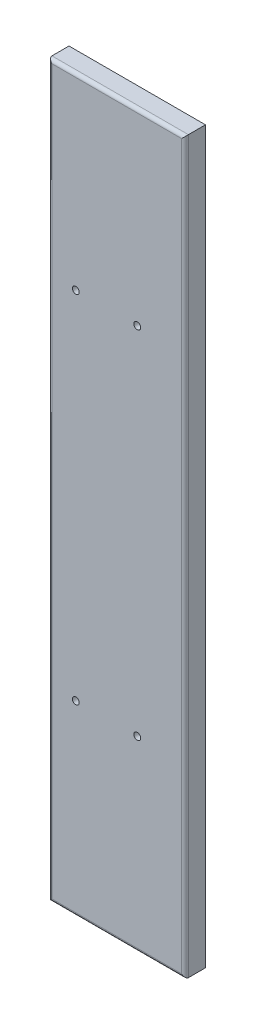
SolidWorks part; units mm, degrees
material "Pine"
ref_plane "Front Plane" through (0, 0, 0) normal (0, 0, 1) x (1, 0, 0)
ref_plane "Top Plane" through (0, 0, 0) normal (0, 1, 0) x (1, 0, 0)
ref_plane "Right Plane" through (0, 0, 0) normal (1, 0, 0) x (0, 0, -1)
sketch "Sketch1" plane through (0, 0, 0) normal (0, 0, 1) x (1, 0, 0)
  line L0 (-50.8, 25.4) -> (-53.975, 25.4)
  line L2 (-53.975, 174.625) -> (73.025, 174.625)
  line L3 (73.025, 174.625) -> (73.025, -504.825)
  line L4 (73.025, -504.825) -> (-53.975, -504.825)
  line L6 (-53.975, -504.825) -> (-53.975, 174.625)
extrude "Boss-Extrude1" add sketch "Sketch1" along normal blind 19.05 contours L3 L4 L6 L2
hole_wizard "1/4 (0.25) Diameter Hole1" positions "Sketch3" profile "Sketch4" hole size "1/4" standard "ANSI Inch" end condition through all
sketch "Sketch3" plane through (0, 0, 19.05) normal (0, 0, 1) x (1, 0, 0)
  point P0 (-28.575, 0)
  point P3 (28.575, 0)
  point P6 (-28.575, -330.9118)
  point P9 (28.575, -330.9118)
sketch "Sketch4" plane through (-28.575, 0, 19.05) normal (1, 0, 0) x (0, -1, 0)
  line L0 (0, 0) -> (0, 19.05)
  line L1 (0, 19.05) -> (3.175, 19.05)
  line L2 (3.175, 19.05) -> (3.175, 0)
  line L5 (3.175, 0) -> (0, 0)
  line L11 (0, -6.35) -> (0, 107.95) construction
  dimension "Thru Hole Dia." = 6.35
  dimension "Thru Hole Depth" = 19.05
fillet "Fillet1" radius 3.175 4 edges at (9.525, 174.625, 19.05) (9.525, -504.825, 19.05) (73.025, -165.1, 19.05) (-53.975, -165.1, 19.05)
